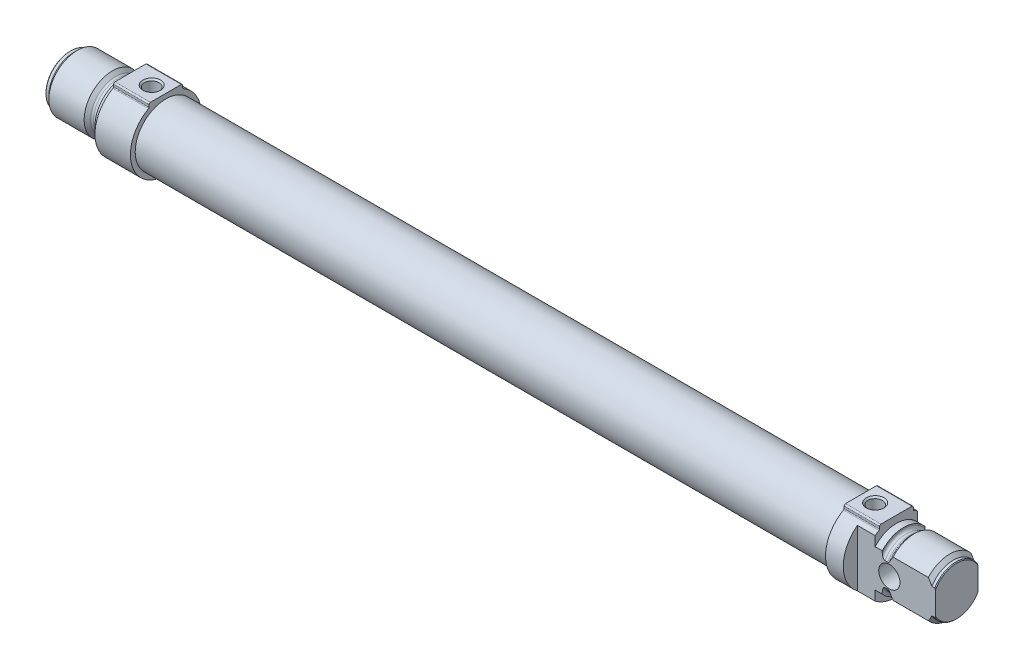
SolidWorks part; units mm, degrees
ref_plane "Ebene vorne" through (0, 0, 0) normal (0, 0, 1) x (1, 0, 0)
ref_plane "Ebene oben" through (0, 0, 0) normal (0, 1, 0) x (1, 0, 0)
ref_plane "Ebene rechts" through (0, 0, 0) normal (1, 0, 0) x (0, 0, -1)
sketch "Skizze1" plane through (0, 0, 0) normal (0, 0, 1) x (1, 0, 0)
  line L0 (0, 0) -> (0, 6.8)
  line L1 (0, 6.8) -> (0.2, 7)
  line L2 (0.2, 7) -> (1, 7)
  line L3 (1, 7) -> (2, 8)
  line L4 (2, 8) -> (11.95, 8)
  line L5 (11.95, 8) -> (12.8657, 7.0843)
  line L6 (13.4314, 6.85) -> (14.2, 6.85)
  line L7 (15, 7.65) -> (15, 8)
  line L8 (15, 8) -> (17, 8)
  line L9 (17, 8) -> (17, 0)
  line L10 (17, 0) -> (0, 0)
  line L11 (17, 0) -> (0, 0) construction
  arc A0 (12.8657, 7.0843) -> (13.4314, 6.85) centre (13.4314, 7.65) ccw
  arc A1 (14.2, 6.85) -> (15, 7.65) centre (14.2, 7.65) ccw
revolve "Rotation1" add sketch "Skizze1" angle 360 about L11 reverse direction yes
cosmetic thread "Gewindedarstellung1" parameters "D1"=10.87, "D2"=14.16
ref_plane "Ebene1" through (21.1, 0, 0) normal (1, 0, 0) x (0, 0, -1)
ref_plane "Ebene2" through (9, 0, 0) normal (1, 0, 0) x (0, 0, -1)
ref_plane "Ebene3" through (0, -11, 0) normal (0, 1, 0) x (1, 0, 0)
ref_plane "Ebene4" through (0, 11, 0) normal (0, 1, 0) x (1, 0, 0)
ref_plane "Ebene5" through (0, 0, 0) normal (0, 1, 0) x (1, 0, 0)
ref_plane "Ebene6" through (0, 0, 0) normal (0, 1, 0) x (1, 0, 0)
ref_plane "Ebene7" through (17, 0, 0) normal (1, 0, 0) x (0, 0, -1)
ref_plane "Ebene8" through (17, 0, 0) normal (1, 0, 0) x (0, 0, -1)
ref_plane "Ebene9" through (27, 0, 0) normal (1, 0, 0) x (0, 0, -1)
ref_plane "Ebene10" through (17, 0, 0) normal (1, 0, 0) x (0, 0, -1)
ref_plane "Ebene11" through (17, 0, 0) normal (1, 0, 0) x (0, 0, -1)
sketch "Skizze2" plane through (17, 0, 0) normal (1, 0, 0) x (0, 0, -1)
  line L0 (4.75, 8.9771) -> (4.75, 9.6)
  line L1 (4.35, 10) -> (-4.35, 10)
  line L2 (-4.75, 9.6) -> (-4.75, 8.9771)
  arc A0 (-4.9029, 8.7156) -> (4.9029, 8.7156) centre (0, 0) ccw
  arc A1 (4.9029, 8.7156) -> (4.75, 8.9771) centre (5.05, 8.9771) cw
  arc A2 (4.75, 9.6) -> (4.35, 10) centre (4.35, 9.6) ccw
  arc A3 (-4.35, 10) -> (-4.75, 9.6) centre (-4.35, 9.6) ccw
  arc A4 (-4.75, 8.9771) -> (-4.9029, 8.7156) centre (-5.05, 8.9771) cw
extrude "Aufsatz-Linear austragen1" add sketch "Skizze2" along normal blind 10
ref_plane "Ebene12" through (23, 0, 0) normal (1, 0, 0) x (0, 0, -1)
sketch "Skizze3" plane through (23, 0, 0) normal (1, 0, 0) x (0, 0, -1)
  line L0 (6.5, 9.5) -> (8.25, 9.5)
  line L1 (8.25, 9.5) -> (8.25, 5.4)
  line L2 (8.25, 5.4) -> (8, 5.4)
  line L3 (8, 5.4) -> (8, 5.3)
  line L4 (8, 5.3) -> (7.8, 5.5)
  line L5 (7.8, 5.5) -> (6.5, 5.5)
  line L6 (6.5, 5.5) -> (6.5, 9.5)
  line L7 (6.5, 5.5) -> (6.5, 9.5) construction
revolve "Schnitt-Rotation1" cut sketch "Skizze3" angle 360 about L7 reverse direction yes
ref_plane "Ebene13" through (0, 0, 0) normal (0, 0, 1) x (1, 0, 0)
ref_plane "Ebene14" through (0, 0, -6.5) normal (0, 0, 1) x (1, 0, 0)
ref_plane "Ebene15" through (0, 0, 0) normal (0, 1, 0) x (1, 0, 0)
ref_plane "Ebene16" through (0, 5.5, 0) normal (0, 1, 0) x (1, 0, 0)
sketch "Skizze4" plane through (0, 5.5, 0) normal (0, 1, 0) x (1, 0, 0)
  line L0 (23.3, 5.0303) -> (23.3, 7.9697)
  line L1 (22.7, 7.9697) -> (22.7, 5.0303)
  arc A0 (22.7, 5.0303) -> (23.3, 5.0303) centre (23, 6.5) ccw
  arc A1 (23.3, 7.9697) -> (22.7, 7.9697) centre (23, 6.5) ccw
extrude "Schnitt-Linear austragen1" cut sketch "Skizze4" against normal blind 0.7
ref_plane "Ebene17" through (0, 0, -6.6) normal (0, 0, 1) x (1, 0, 0)
ref_plane "Ebene18" through (0, 0, 0) normal (0, 1, 0) x (1, 0, 0)
ref_plane "Ebene19" through (0, 5.5, 0) normal (0, 1, 0) x (1, 0, 0)
ref_plane "Ebene20" through (0, 6.4628, -1.1396) normal (0, 0.9848, -0.1736) x (1, 0, 0)
ref_plane "Ebene21" through (0, 4.9856, -0.8791) normal (0, 0.9848, -0.1736) x (1, 0, 0)
sketch "Skizze5" plane through (0, 0, 0) normal (0, 0, 1) x (1, 0, 0)
  line L0 (27, 0) -> (27, 8.65)
  line L1 (27, 8.65) -> (223, 8.65)
  line L2 (223, 8.65) -> (223, 0)
  line L3 (223, 0) -> (27, 0)
  line L4 (223, 0) -> (27, 0) construction
revolve "Rotation2" add sketch "Skizze5" angle 360 about L4 reverse direction yes
ref_plane "Ebene22" through (223, 0, 0) normal (1, 0, 0) x (0, 0, -1)
sketch "Skizze6" plane through (223, 0, 0) normal (1, 0, 0) x (0, 0, -1)
  line L0 (4.75, 8.9771) -> (4.75, 9.6)
  line L1 (4.35, 10) -> (-4.35, 10)
  line L2 (-4.75, 9.6) -> (-4.75, 8.9771)
  arc A0 (-4.9029, 8.7156) -> (4.9029, 8.7156) centre (0, 0) ccw
  arc A1 (4.9029, 8.7156) -> (4.75, 8.9771) centre (5.05, 8.9771) cw
  arc A2 (4.75, 9.6) -> (4.35, 10) centre (4.35, 9.6) ccw
  arc A3 (-4.35, 10) -> (-4.75, 9.6) centre (-4.35, 9.6) ccw
  arc A4 (-4.75, 8.9771) -> (-4.9029, 8.7156) centre (-5.05, 8.9771) cw
extrude "Aufsatz-Linear austragen2" add sketch "Skizze6" along normal blind 10
ref_plane "Ebene23" through (225.35, 0, 0) normal (1, 0, 0) x (0, 0, -1)
ref_plane "Ebene24" through (227, 0, 0) normal (1, 0, 0) x (0, 0, -1)
ref_plane "Ebene25" through (0, 0, 6.6) normal (0, 0, 1) x (1, 0, 0)
ref_plane "Ebene26" through (0, 0, 0) normal (0, 1, 0) x (1, 0, 0)
ref_plane "Ebene27" through (0, 5.5, 0) normal (0, 1, 0) x (1, 0, 0)
ref_plane "Ebene28" through (0, 6.4628, 1.1396) normal (0, 0.9848, 0.1736) x (1, 0, 0)
ref_plane "Ebene29" through (0, 4.9856, 0.8791) normal (0, 0.9848, 0.1736) x (1, 0, 0)
sketch "Skizze7" plane through (225.35, 0, 0) normal (1, 0, 0) x (0, 0, -1)
  line L0 (6.5, 9.5) -> (8.25, 9.5)
  line L1 (8.25, 9.5) -> (8.25, 5.4)
  line L2 (8.25, 5.4) -> (8, 5.4)
  line L3 (8, 5.4) -> (8, 5.3)
  line L4 (8, 5.3) -> (7.8, 5.5)
  line L5 (7.8, 5.5) -> (6.5, 5.5)
  line L6 (6.5, 5.5) -> (6.5, 9.5)
  line L7 (6.5, 5.5) -> (6.5, 9.5) construction
revolve "Schnitt-Rotation2" cut sketch "Skizze7" angle 360 about L7 reverse direction yes
sketch "Skizze8" plane through (0, 5.5, 0) normal (0, 1, 0) x (1, 0, 0)
  line L0 (225.65, 5.0303) -> (225.65, 7.9697)
  line L1 (225.05, 7.9697) -> (225.05, 5.0303)
  arc A0 (225.05, 5.0303) -> (225.65, 5.0303) centre (225.35, 6.5) ccw
  arc A1 (225.65, 7.9697) -> (225.05, 7.9697) centre (225.35, 6.5) ccw
extrude "Schnitt-Linear austragen2" cut sketch "Skizze8" against normal blind 0.7
ref_plane "Ebene30" through (271, 0, 0) normal (1, 0, 0) x (0, 0, -1)
sketch "Skizze9" plane through (0, 0, 0) normal (0, 0, 1) x (1, 0, 0)
  line L0 (233, 0) -> (233, 8)
  line L1 (233, 8) -> (235, 8)
  line L2 (235, 8) -> (235, 7.65)
  line L3 (235.8, 6.85) -> (236.5686, 6.85)
  line L4 (237.1343, 7.0843) -> (238.05, 8)
  line L5 (238.05, 8) -> (248, 8)
  line L6 (248, 8) -> (249, 7)
  line L7 (249, 7) -> (249.8, 7)
  line L8 (249.8, 7) -> (250, 6.8)
  line L9 (250, 6.8) -> (250, 0)
  line L10 (250, 0) -> (233, 0)
  line L11 (250, 0) -> (233, 0) construction
  arc A0 (235, 7.65) -> (235.8, 6.85) centre (235.8, 7.65) ccw
  arc A1 (236.5686, 6.85) -> (237.1343, 7.0843) centre (236.5686, 7.65) ccw
revolve "Rotation3" add sketch "Skizze9" angle 360 about L11 reverse direction yes
cosmetic thread "Gewindedarstellung2" parameters "D1"=9.87, "D2"=14.16
ref_plane "Ebene31" through (261, 0, 0) normal (1, 0, 0) x (0, 0, -1)
ref_plane "Ebene32" through (271, 0, 0) normal (1, 0, 0) x (0, 0, -1)
ref_plane "Ebene33" through (271, 0, 0) normal (1, 0, 0) x (0, 0, -1)
sketch "Skizze10" plane through (0, 0, 0) normal (0, 1, 0) x (1, 0, 0)
  line L0 (228, 18) -> (228, 6)
  line L1 (228, 6) -> (250, 6)
  line L2 (250, 6) -> (250, -6)
  line L3 (250, -6) -> (228, -6)
  line L4 (228, -6) -> (228, -18)
  line L5 (228, -18) -> (262, -18)
  line L6 (262, -18) -> (262, 18)
  line L7 (262, 18) -> (228, 18)
extrude "Schnitt-Linear austragen3" cut sketch "Skizze10" along normal blind 10 and the other way blind 10
ref_plane "Ebene34" through (237, 0, 0) normal (1, 0, 0) x (0, 0, -1)
hole_wizard "Bohrung1" positions "Skizze12" profile "Skizze11" legacy
sketch "Skizze12" plane through (0, 0, -6) normal (0, 0, -1) x (-1, 0, 0)
  point P0 (-237, 0)
sketch "Skizze11" plane through (237, 0, -6) normal (1, 0, 0) x (0, 1, 0)
  line L0 (0, 0) -> (0, 12)
  line L1 (0, 12) -> (3, 12)
  line L2 (3, 12) -> (3, 0)
  line L3 (3, 0) -> (0, 0)
  line L4 (0, 110) -> (0, -10) construction
  dimension "Durchmesser" = 6
  dimension "Tiefe" = 12
hole_wizard "Bohrung2" positions "Skizze14" profile "Skizze13" legacy
sketch "Skizze14" plane through (0, 10, 0) normal (0, 1, 0) x (1, 0, 0)
  point P0 (23, 0)
sketch "Skizze13" plane through (23, 10, 0) normal (1, 0, 0) x (0, 0, 1)
  line L0 (0, 0) -> (0, 10)
  line L1 (0, 10) -> (2.067, 10)
  line L2 (2.067, 10) -> (2.067, 0.433)
  line L3 (2.067, 0.433) -> (2.5, 0)
  line L4 (2.5, 0) -> (0, 0)
  line L5 (0, -6.4453) -> (0, 115.525) construction
  line L6 (-2.067, 0.433) -> (-2.5, 0) construction
  dimension "Durchmesser" = 4.134
  dimension "Tiefe" = 10
  dimension "Senkwinkel1" = 90
  dimension "Senkdurchmesser3" = 5
cosmetic thread "Gewindedarstellung3" parameters "D1"=7, "D2"=5
hole_wizard "Bohrung3" positions "Skizze16" profile "Skizze15" legacy
sketch "Skizze16" plane through (0, 10, 0) normal (0, 1, 0) x (1, 0, 0)
  point P0 (227, 0)
sketch "Skizze15" plane through (227, 10, 0) normal (1, 0, 0) x (0, 0, 1)
  line L0 (0, 0) -> (0, 10)
  line L1 (0, 10) -> (2.067, 10)
  line L2 (2.067, 10) -> (2.067, 0.433)
  line L3 (2.067, 0.433) -> (2.5, 0)
  line L4 (2.5, 0) -> (0, 0)
  line L5 (0, -6.4453) -> (0, 115.525) construction
  line L6 (-2.067, 0.433) -> (-2.5, 0) construction
  dimension "Durchmesser" = 4.134
  dimension "Tiefe" = 10
  dimension "Senkwinkel1" = 90
  dimension "Senkdurchmesser3" = 5
cosmetic thread "Gewindedarstellung4" parameters "D1"=7, "D2"=5
sketch "Skizze17" plane through (0, 0, 0) normal (0, 0, 1) x (1, 0, 0)
  line L0 (-5, 0) -> (-5, 3)
  line L1 (-5, 3) -> (41.2, 3)
  line L2 (41.2, 3) -> (41.2, 8)
  line L3 (41.2, 8) -> (205.2, 8)
  line L4 (205.2, 8) -> (205.2, 0)
  line L5 (205.2, 0) -> (-5, 0)
  line L6 (205.2, 0) -> (-5, 0) construction
revolve "Schnitt-Rotation3" cut sketch "Skizze17" angle 360 about L6 reverse direction yes
ref_plane "Ebene35" through (-5, 0, 0) normal (1, 0, 0) x (0, 0, -1)
ref_plane "Ebene36" through (0, 10, 0) normal (0, 1, 0) x (1, 0, 0)
ref_plane "Ebene37" through (7, 0, 0) normal (1, 0, 0) x (0, 0, -1)
ref_plane "Ebene38" through (0, 0, 0) normal (1, 0, 0) x (0, 0, -1)
ref_plane "Ebene39" through (17, 0, 0) normal (1, 0, 0) x (0, 0, -1)
ref_plane "Ebene40" through (233, 0, 0) normal (1, 0, 0) x (0, 0, -1)
ref_plane "Ebene41" through (17, 0, 0) normal (1, 0, 0) x (0, 0, -1)
ref_plane "Ebene42" through (0, 10, 0) normal (0, 1, 0) x (1, 0, 0)
ref_plane "Ebene43" through (36.5, 0, 0) normal (1, 0, 0) x (0, 0, -1)
ref_plane "Ebene44" through (213.5, 0, 0) normal (1, 0, 0) x (0, 0, -1)
ref_plane "Ebene45" through (0, 0, 0) normal (0, 0, 1) x (1, 0, 0)
ref_plane "Ebene46" through (17, 0, 0) normal (1, 0, 0) x (0, 0, -1)
ref_plane "Ebene47" through (0, 10, 0) normal (0, 1, 0) x (1, 0, 0)
ref_plane "FDT_FRONT XY" through (17, 0, 0) normal (1, 0, 0) x (0, 0, -1)
ref_plane "FDT_FRONT XZ" through (0, 0, 0) normal (0, -1, 0) x (-1, 0, 0)
ref_plane "FDT_FRONT YZ" through (0, 0, 0) normal (0, 0, -1) x (-1, 0, 0)
ref_axis "FDT_FRONT X" through (17, 0, 80.9) along (0, 0, -1)
ref_axis "FDT_FRONT Y" through (17, -50, 0) along (0, 1, 0)
ref_axis "FDT_FRONT Z" through (80.9, 0, 0) along (-1, 0, 0)
sketch3d "FDT_FRONT"
  point P0 (17, 0, 0)
ref_plane "FDT_QSFRONT XY" through (0, 10, 0) normal (0, 1, 0) x (1, 0, 0)
ref_plane "FDT_QSFRONT XZ" through (23, 0, 0) normal (-1, 0, 0) x (0, 0, 1)
ref_plane "FDT_QSFRONT YZ" through (0, 0, 0) normal (0, 0, 1) x (1, 0, 0)
ref_axis "FDT_QSFRONT X" through (23, 10, -50) along (0, 0, 1)
ref_axis "FDT_QSFRONT Y" through (-80.9, 10, 0) along (1, 0, 0)
ref_axis "FDT_QSFRONT Z" through (23, 50, 0) along (0, -1, 0)
sketch3d "FDT_QSFRONT"
  point P0 (23, 10, 0)
ref_plane "FDT_QSREAR XY" through (0, 10, 0) normal (0, 1, 0) x (1, 0, 0)
ref_plane "FDT_QSREAR XZ" through (227, 0, 0) normal (-1, 0, 0) x (0, 0, 1)
ref_plane "FDT_QSREAR YZ" through (0, 0, 0) normal (0, 0, 1) x (1, 0, 0)
ref_axis "FDT_QSREAR X" through (227, 10, -50) along (0, 0, 1)
ref_axis "FDT_QSREAR Y" through (-80.9, 10, 0) along (1, 0, 0)
ref_axis "FDT_QSREAR Z" through (227, 50, 0) along (0, -1, 0)
sketch3d "FDT_QSREAR"
  point P0 (227, 10, 0)
ref_plane "FDT_REAR XY" through (233, 0, 0) normal (-1, 0, 0) x (0, 0, 1)
ref_plane "FDT_REAR XZ" through (0, 0, 0) normal (0, 1, 0) x (1, 0, 0)
ref_plane "FDT_REAR YZ" through (0, 0, 0) normal (0, 0, -1) x (-1, 0, 0)
ref_axis "FDT_REAR X" through (233, 0, 80.9) along (0, 0, -1)
ref_axis "FDT_REAR Y" through (233, 50, 0) along (0, -1, 0)
ref_axis "FDT_REAR Z" through (-80.9, 0, 0) along (1, 0, 0)
sketch3d "FDT_REAR"
  point P0 (233, 0, 0)
ref_plane "FDT_SMBR1 XY" through (36.5, 0, 0) normal (-1, 0, 0) x (0, 0, 1)
ref_plane "FDT_SMBR1 XZ" through (0, 0, 0) normal (0, -1, 0) x (-1, 0, 0)
ref_plane "FDT_SMBR1 YZ" through (0, 0, 0) normal (0, 0, 1) x (1, 0, 0)
ref_axis "FDT_SMBR1 X" through (36.5, 0, -80.9) along (0, 0, 1)
ref_axis "FDT_SMBR1 Y" through (36.5, -50, 0) along (0, 1, 0)
ref_axis "FDT_SMBR1 Z" through (-80.9, 0, 0) along (1, 0, 0)
sketch3d "FDT_SMBR1"
  point P0 (36.5, 0, 0)
ref_plane "FDT_SMBR2 XY" through (213.5, 0, 0) normal (-1, 0, 0) x (0, 0, 1)
ref_plane "FDT_SMBR2 XZ" through (0, 0, 0) normal (0, -1, 0) x (-1, 0, 0)
ref_plane "FDT_SMBR2 YZ" through (0, 0, 0) normal (0, 0, 1) x (1, 0, 0)
ref_axis "FDT_SMBR2 X" through (213.5, 0, -80.9) along (0, 0, 1)
ref_axis "FDT_SMBR2 Y" through (213.5, -50, 0) along (0, 1, 0)
ref_axis "FDT_SMBR2 Z" through (-80.9, 0, 0) along (1, 0, 0)
sketch3d "FDT_SMBR2"
  point P0 (213.5, 0, 0)
ref_plane "FDT_SWIVELAXIS XY" through (0, 0, 0) normal (0, 0, 1) x (1, 0, 0)
ref_plane "FDT_SWIVELAXIS XZ" through (0, 0, 0) normal (0, -1, 0) x (-1, 0, 0)
ref_plane "FDT_SWIVELAXIS YZ" through (237, 0, 0) normal (1, 0, 0) x (0, 0, -1)
ref_axis "FDT_SWIVELAXIS X" through (-80.9, 0, 0) along (1, 0, 0)
ref_axis "FDT_SWIVELAXIS Y" through (237, -50, 0) along (0, 1, 0)
ref_axis "FDT_SWIVELAXIS Z" through (237, 0, 80.9) along (0, 0, -1)
sketch3d "FDT_SWIVELAXIS"
  point P0 (237, 0, 0)
ref_plane "NUT XY" through (7, 0, 0) normal (1, 0, 0) x (0, 0, -1)
ref_plane "NUT XZ" through (0, 0, 0) normal (0, -1, 0) x (-1, 0, 0)
ref_plane "NUT YZ" through (0, 0, 0) normal (0, 0, -1) x (-1, 0, 0)
ref_axis "NUT X" through (7, 0, 80.9) along (0, 0, -1)
ref_axis "NUT Y" through (7, -50, 0) along (0, 1, 0)
ref_axis "NUT Z" through (80.9, 0, 0) along (-1, 0, 0)
sketch3d "NUT"
  point P0 (7, 0, 0)
ref_plane "ZR XY" through (0, 0, 0) normal (1, 0, 0) x (0, 0, -1)
ref_plane "ZR XZ" through (0, 0, 0) normal (0, -1, 0) x (-1, 0, 0)
ref_plane "ZR YZ" through (0, 0, 0) normal (0, 0, -1) x (-1, 0, 0)
ref_axis "ZR X" through (0, 0, 80.9) along (0, 0, -1)
ref_axis "ZR Y" through (0, -50, 0) along (0, 1, 0)
ref_axis "ZR Z" through (80.9, 0, 0) along (-1, 0, 0)
sketch3d "ZR"
  point P0 (0, 0, 0)
ref_plane "ZYL XY" through (17, 0, 0) normal (1, 0, 0) x (0, 0, -1)
ref_plane "ZYL XZ" through (0, 0, 0) normal (0, -1, 0) x (-1, 0, 0)
ref_plane "ZYL YZ" through (0, 0, 0) normal (0, 0, -1) x (-1, 0, 0)
ref_axis "ZYL X" through (17, 0, 80.9) along (0, 0, -1)
ref_axis "ZYL Y" through (17, -50, 0) along (0, 1, 0)
ref_axis "ZYL Z" through (80.9, 0, 0) along (-1, 0, 0)
sketch3d "ZYL"
  point P0 (17, 0, 0)
